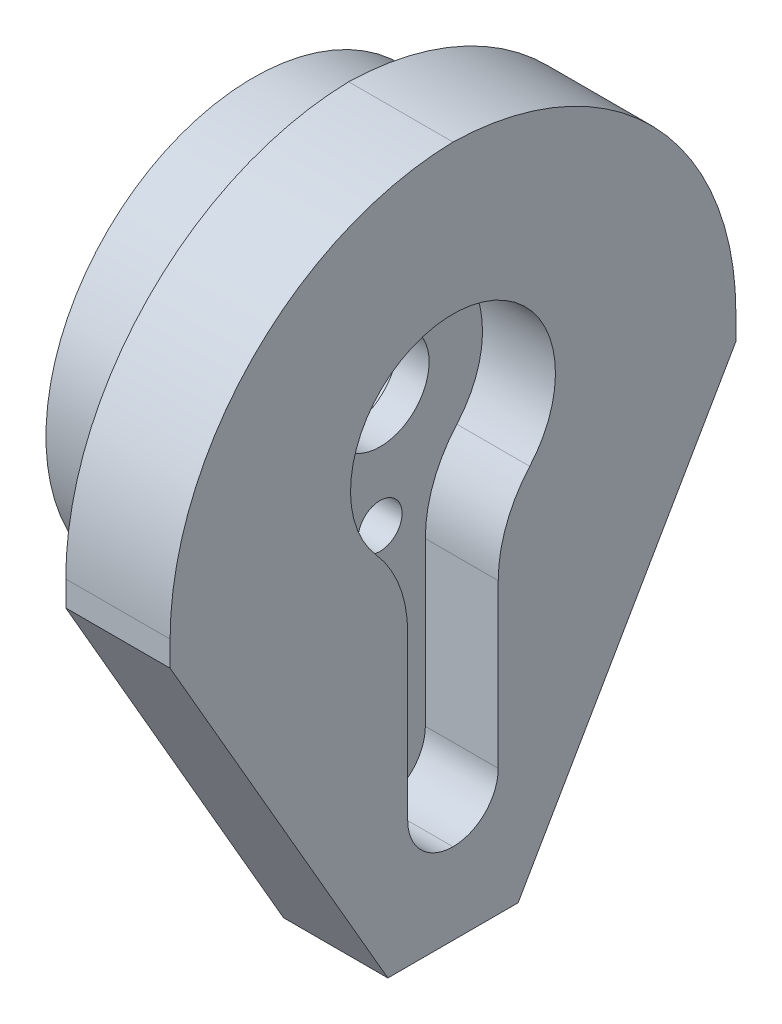
SolidWorks part; units mm, degrees
ref_plane "Front Plane" through (0, 0, 0) normal (0, 0, 1) x (1, 0, 0)
ref_plane "Top Plane" through (0, 0, 0) normal (0, 1, 0) x (1, 0, 0)
ref_plane "Right Plane" through (0, 0, 0) normal (1, 0, 0) x (0, 0, -1)
sketch "Sketch1" plane through (0, 0, 0) normal (1, 0, 0) x (0, 0, -1)
  line L1 (-10, 10) -> (10, 10)
  line L2 (-10, 10) -> (-10, -10)
  line L3 (-10, -10) -> (10, -10)
  line L4 (10, 10) -> (10, -10)
  line L5 (-10, 10) -> (10, -10) construction
  line L6 (-10, -10) -> (10, 10) construction
  point P0 (0, 0)
  dimension "D1" = 20
  dimension "D2" = 20
extrude "Boss-Extrude1" add sketch "Sketch1" along normal blind 20
sketch "Sketch2" plane through (20, 0, 0) normal (1, 0, 0) x (0, 0, -1)
  line L1 (-22.5, 35) -> (22.5, 35)
  line L2 (-22.5, 35) -> (-22.5, -35)
  line L3 (-22.5, -35) -> (22.5, -35)
  line L4 (22.5, 35) -> (22.5, -35)
  line L5 (-22.5, 35) -> (22.5, -35) construction
  line L6 (-22.5, -35) -> (22.5, 35) construction
  point P0 (0, 0)
  dimension "D1" = 45
  dimension "D2" = 70
extrude "Boss-Extrude2" add sketch "Sketch2" along normal blind 8.3
sketch "Sketch4" plane through (28.3, 0, 0) normal (1, 0, 0) x (0, 0, -1)
  line L0 (0, 7.65) -> (0, 8.1702) construction
  line L1 (7.65, 7.65) -> (-7.65, 7.65) construction
  line L17 (3.6, -26.55) -> (-3.6, -26.55) construction
  line L18 (-7.65, 7.65) -> (7.65, 7.65) construction
  line L22 (-7.65, 7.65) -> (-7.65, -27.55) construction
  line L23 (-7.65, -27.55) -> (7.65, -27.55) construction
  line L24 (7.65, 7.65) -> (7.65, -27.55) construction
  line L25 (-7.65, 7.65) -> (7.65, -27.55) construction
  line L26 (-7.65, -27.55) -> (7.65, 7.65) construction
  line L27 (3.6, -26.55) -> (3.6, -28.55) construction
  line L28 (3.6, -28.55) -> (-3.6, -28.55) construction
  line L29 (-3.6, -26.55) -> (-3.6, -28.55) construction
  line L30 (3.6, -26.55) -> (-3.6, -28.55) construction
  line L31 (3.6, -28.55) -> (-3.6, -26.55) construction
  line L34 (3.6, -28.55) -> (-3.6, -28.55)
  line L35 (-3.6, -28.55) -> (-3.6, -7.3118)
  line L36 (3.6, -28.55) -> (3.6, -7.3118)
  arc A1 (3.6, -6.75) -> (-3.6, -6.75) centre (0, 0) ccw construction
  arc A2 (3.6, -7.3118) -> (-3.6, -7.3118) centre (0, 0) ccw
  point P1 (0, -27.55)
  point P7 (0, -13.75)
  point P10 (0, 7.65)
  point P14 (0, -9.95)
  dimension "D1" = 15.3
  dimension "D5" = 2
  dimension "D2" = 15.3
  dimension "D3" = 35.2
  dimension "D4" = 7.2
extrude "Cut-Extrude1" cut sketch "Sketch4" against normal blind 5.8
fillet "Fillet1" radius 3.6 2 edges at (25.4, -28.55, 3.6) (25.4, -28.55, -3.6)
fillet "Fillet2" radius 10 2 edges at (25.4, -7.3118, 3.6) (25.4, -7.3118, -3.6)
sketch "Sketch5" plane through (0, 0, 0) normal (-1, 0, 0) x (0, 0, 1)
  circle A0 centre (0, 0) radius 3.9
  dimension "D1" = 7.8
extrude "Cut-Extrude2" cut sketch "Sketch5" against normal through all
sketch "Sketch6" plane through (22.5, 0, 0) normal (1, 0, 0) x (0, 0, -1)
  line L0 (0, -19.35) -> (0, 0) construction
  line L1 (0, -25.65) -> (0, -23.15) construction
  line L2 (0, -23.15) -> (0, -21.85) construction
  line L3 (0, -21.85) -> (0, -19.35) construction
  line L5 (0, 0) -> (1.164, 0) construction
  line L6 (0, 0) -> (0, -9.35) construction
  line L7 (0, -9.35) -> (1.164, -9.35) construction
  line L8 (1.164, 0) -> (1.164, -9.35) construction
  line L9 (0, 0) -> (1.164, -9.35) construction
  line L10 (0, -9.35) -> (1.164, 0) construction
  circle A0 centre (0, -20.6) radius 1.75
  circle A1 centre (0, -9.35) radius 1.75
  point P11 (0.582, -4.675)
  dimension "D5" = 3.5
  dimension "D6" = 9.35
  dimension "D7" = 3.5
  dimension "D1" = 19.35
  dimension "D2" = 2.5
  dimension "D3" = 1.3
  dimension "D4" = 2.5
extrude "Cut-Extrude3" cut sketch "Sketch6" against normal up to next
sketch "Sketch13" plane through (0, 0, 0) normal (-1, 0, 0) x (0, 0, 1)
  line L1 (-10, 10) -> (10, 10)
  line L2 (-10, 10) -> (-10, -10)
  line L3 (-10, -10) -> (10, -10)
  line L4 (10, 10) -> (10, -10)
extrude "Cut-Extrude9" cut sketch "Sketch13" against normal up to surface (20 mm away) up to face at (20, -20.6, -1.75)
sketch "Sketch14" plane through (20, 0, 0) normal (-1, 0, 0) x (0, 0, 1)
  line L0 (0, -11.1) -> (0, -18.85) construction
  circle A0 centre (0, -9.35) radius 1.75 construction
  circle A1 centre (0, -20.6) radius 1.75 construction
  circle A3 centre (0, 0) radius 16.475
  point P7 (0, -14.975)
extrude "Boss-Extrude3" add sketch "Sketch14" along normal blind 7.6 contours A3
sketch "Sketch15" plane through (0, 35, 0) normal (0, 1, 0) x (1, 0, 0)
  line L1 (20, 22.5) -> (28.3, 22.5)
  line L2 (20, 22.5) -> (20, -22.5)
  line L3 (20, -22.5) -> (28.3, -22.5)
  line L4 (28.3, 22.5) -> (28.3, -22.5)
extrude "Cut-Extrude10" cut sketch "Sketch15" against normal blind 15
fillet "Fillet3" radius 23 2 edges at (24.15, 20, -22.5) (24.15, 20, 22.5)
chamfer "Chamfer1" distance 30 angle 30 1 edges at (24.15, -35, 22.5) first distance on face at (24.15, -19, 22.5)
chamfer "Chamfer2" distance 30 angle 30 1 edges at (24.15, -35, -22.5) first distance on face at (24.15, -19, -22.5)
sketch "Sketch16" plane through (12.4, 0, 0) normal (-1, 0, 0) x (0, 0, 1)
  circle A4 centre (0, 0) radius 13.475
  circle A5 centre (0, 0) radius 13.475
  dimension "D1" = 3
extrude "Cut-Extrude11" cut sketch "Sketch16" against normal blind 7.6
fillet "Fillet4" radius 1 2 edges at (20, 0, 13.475) (20, 0, -16.475)
